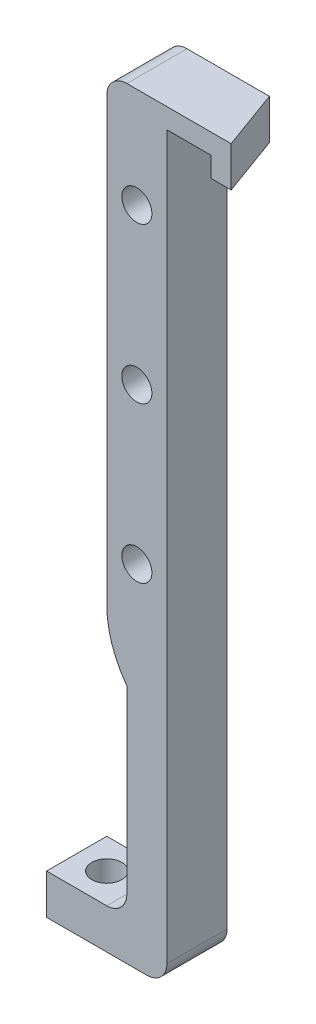
SolidWorks part; units mm, degrees
ref_plane "Front Plane" through (0, 0, 0) normal (0, 0, 1) x (1, 0, 0)
ref_plane "Top Plane" through (0, 0, 0) normal (0, 1, 0) x (1, 0, 0)
ref_plane "Right Plane" through (0, 0, 0) normal (1, 0, 0) x (0, 0, -1)
sketch "Sketch1" plane through (0, 0, 0) normal (1, 0, 0) x (0, 0, -1)
  line L1 (0, 0) -> (7.62, 0)
  line L2 (0, 0) -> (0, 96.52)
  line L3 (0, 96.52) -> (7.62, 96.52)
  line L4 (7.62, 0) -> (7.62, 96.52)
  dimension "D1" = 7.62
  dimension "D2" = 96.52
extrude "Boss-Extrude1" add sketch "Sketch1" along normal blind 7.62
sketch "Sketch2" plane through (0, 0, 0) normal (-1, 0, 0) x (0, 0, 1)
  line L0 (-7.62, 0) -> (-7.62, 96.52) construction
  line L1 (0, 0) -> (-7.62, 0)
  line L2 (0, 0) -> (0, 5.08)
  line L3 (0, 5.08) -> (-7.62, 5.08)
  line L4 (-7.62, 0) -> (-7.62, 5.08)
  dimension "D1" = 5.08
extrude "Boss-Extrude2" add sketch "Sketch2" along normal blind 7.62
sketch "Sketch4" plane through (7.62, 0, 0) normal (1, 0, 0) x (0, 0, -1)
  line L0 (7.62, 0) -> (7.62, 96.52) construction
  line L1 (0, 96.52) -> (7.62, 96.52)
  line L2 (0, 96.52) -> (0, 93.98)
  line L3 (0, 93.98) -> (7.62, 93.98)
  line L4 (7.62, 96.52) -> (7.62, 93.98)
  dimension "D1" = 2.54
extrude "Boss-Extrude3" add sketch "Sketch4" along normal blind 8.128
sketch "Sketch5" plane through (0, 93.98, 0) normal (0, -1, 0) x (1, 0, 0)
  line L1 (15.748, 0) -> (12.9745, -7.62)
  line L2 (15.748, -7.62) -> (7.62, -7.62) construction
  line L3 (15.748, 0) -> (15.748, -7.62) construction
  line L4 (10.4345, -7.62) -> (13.208, 0)
  line L5 (15.748, 0) -> (7.62, 0) construction
  line L6 (15.748, 0) -> (13.208, 0)
  line L7 (10.4345, -7.62) -> (12.9745, -7.62)
  dimension "D1" = 20
  dimension "D2" = 2.54
  dimension "D3" = 20
extrude "Boss-Extrude4" add sketch "Sketch5" along normal blind 2.54
hole_wizard "#6 Clearance Hole1" positions "Sketch7" profile "Sketch6" hole size "#6" standard "ANSI Inch" end condition up to next
sketch "Sketch7" plane through (0, 5.08, 0) normal (0, 1, 0) x (1, 0, 0)
  line L2 (0, 0) -> (0, 7.62) construction
  line L3 (-7.62, 7.62) -> (0, 7.62) construction
  point P0 (-3.81, 3.81)
  dimension "D1" = 3.81
  dimension "D2" = 3.81
sketch "Sketch6" plane through (-3.81, 5.08, -3.81) normal (1, 0, 0) x (0, 0, 1)
  line L0 (0, 0) -> (0, 5.08)
  line L1 (0, 5.08) -> (1.8986, 5.08)
  line L2 (1.8986, 5.08) -> (1.8986, 0)
  line L5 (1.8986, 0) -> (0, 0)
  line L11 (0, -6.35) -> (0, 107.95) construction
  dimension "Thru Hole Dia." = 3.7973
  dimension "Thru Hole Depth" = 5.08
sketch "Sketch8" plane through (0, 93.98, 0) normal (0, -1, 0) x (1, 0, 0)
  line L0 (15.748, -7.62) -> (12.9745, -7.62)
  line L1 (12.9745, -7.62) -> (15.748, 0)
  line L2 (15.748, 0) -> (15.748, -7.62)
extrude "Cut-Extrude1" cut sketch "Sketch8" against normal blind 2.54
ref_plane "Plane1" through (0, 0, -10.16) normal (0, 0, -1) x (-1, 0, 0)
sketch "Sketch12" plane through (0, 0, 0) normal (-1, 0, 0) x (0, 0, 1)
  line L0 (0, 96.52) -> (0, 5.08) construction
  line L1 (-7.62, 5.08) -> (0, 5.08)
  line L2 (-7.62, 5.08) -> (-7.62, 30.48)
  line L3 (-7.62, 30.48) -> (0, 30.48)
  line L4 (0, 5.08) -> (0, 30.48)
  dimension "D1" = 25.4
extrude "Cut-Extrude2" cut sketch "Sketch12" against normal blind 2.54
fillet "Fillet2" radius 12.7 1 edges at (0, 30.48, -3.81)
fillet "Fillet3" radius 2.54 3 edges at (2.54, 5.08, -3.81) (7.62, 0, -3.81) (0, 96.52, -3.81)
sketch "Sketch14" plane through (0, 0, 0) normal (0, 0, 1) x (1, 0, 0)
  line L0 (0, 93.98) -> (0, 38.1) construction
  line L1 (15.748, 96.52) -> (2.54, 96.52) construction
  circle A0 centre (3.81, 83.82) radius 1.905
  circle A1 centre (3.81, 44.45) radius 1.905
  circle A2 centre (3.81, 64.135) radius 1.905
  dimension "D5" = 3.81
  dimension "D6" = 3.81
  dimension "D7" = 3.81
  dimension "D8" = 19.685
  dimension "D1" = 3.81
  dimension "D2" = 3.81
  dimension "D3" = 12.7
  dimension "D4" = 39.37
extrude "Cut-Extrude4" cut sketch "Sketch14" against normal through all
